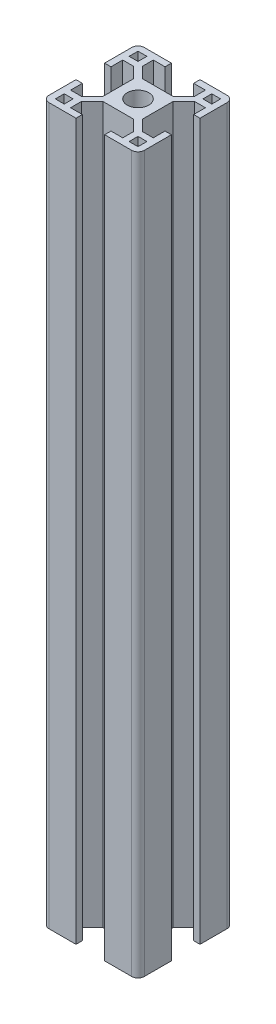
SolidWorks part; units mm, degrees
ref_plane "Front plane" through (0, 0, 0) normal (0, 0, 1) x (1, 0, 0)
ref_plane "Top plane" through (0, 0, 0) normal (0, 1, 0) x (1, 0, 0)
ref_plane "Right plane" through (0, 0, 0) normal (1, 0, 0) x (0, 0, -1)
ref_axis "Axis X" through (0, 0, 0) along (1, 0, 0)
ref_axis "Axis Y" through (0, 0, 0) along (0, 1, 0)
ref_axis "Axis Z" through (0, 0, 0) along (0, 0, 1)
sketch "Sketch1" plane through (0, 0, 0) normal (0, 1, 0) x (1, 0, 0)
  line L1 (-10, 10) -> (10, 10)
  line L2 (-10, 10) -> (-10, -10)
  line L3 (-10, -10) -> (10, -10)
  line L4 (10, 10) -> (10, -10)
  line L5 (-10, 10) -> (10, -10) construction
  line L6 (-10, -10) -> (10, 10) construction
  point P0 (0, 0)
  dimension "D1" = 20
  dimension "D2" = 20
extrude "Extrude1" add sketch "Sketch1" along normal blind 150
sketch "Sketch2" plane through (0, 150, 0) normal (0, 1, 0) x (1, 0, 0)
  line L0 (0, 0) -> (10, 0) construction
  line L1 (10, -10) -> (10, 10) construction
  line L2 (10, 10) -> (-10, 10) construction
  line L3 (8.6667, 3) -> (11.3333, 3)
  line L4 (8.6667, 3) -> (8.6667, -3) construction
  line L5 (8.6667, -3) -> (11.3333, -3)
  line L6 (11.3333, 3) -> (11.3333, -3)
  line L7 (8.6667, 3) -> (11.3333, -3) construction
  line L8 (8.6667, -3) -> (11.3333, 3) construction
  line L9 (6.8, 8.6667) -> (8.6667, 8.6667)
  line L10 (6.8, 8.6667) -> (6.8, 6.8)
  line L11 (6.8, 6.8) -> (8.6667, 6.8)
  line L12 (8.6667, 8.6667) -> (8.6667, 6.8)
  line L13 (6.8, 8.6667) -> (8.6667, 6.8) construction
  line L14 (6.8, 6.8) -> (8.6667, 8.6667) construction
  line L15 (0, 0) -> (10, 10) construction
  line L16 (8.6667, 3) -> (8.6667, 5.4667)
  line L17 (8.6667, 5.4667) -> (6.4095, 5.4667)
  line L18 (6.4095, 5.4667) -> (4.1333, 3.1905)
  line L19 (4.1333, 3.1905) -> (4.1333, -3.1905)
  line L20 (4.1333, -3.1905) -> (6.4095, -5.4667)
  line L21 (6.4095, -5.4667) -> (8.6667, -5.4667)
  line L22 (8.6667, -5.4667) -> (8.6667, -3)
  line L65 (-3.1905, 4.1333) -> (-5.4667, 6.4095)
  line L66 (-5.4667, 6.4095) -> (-5.4667, 8.6667)
  line L67 (-5.4667, 8.6667) -> (-3, 8.6667)
  line L68 (3, 11.3333) -> (-3, 11.3333)
  line L69 (-3, 8.6667) -> (-3, 11.3333)
  line L70 (3, 8.6667) -> (3, 11.3333)
  line L71 (3, 8.6667) -> (5.4667, 8.6667)
  line L72 (5.4667, 8.6667) -> (5.4667, 6.4095)
  line L73 (5.4667, 6.4095) -> (3.1905, 4.1333)
  line L74 (3.1905, 4.1333) -> (-3.1905, 4.1333)
  line L75 (0, 10) -> (0, -10) construction
  line L76 (-10, -10) -> (10, -10) construction
  line L77 (0, 0) -> (-10, 0) construction
  line L78 (-10, 10) -> (-10, -10) construction
  line L79 (8.6667, -8.6667) -> (8.6667, -6.8)
  line L80 (6.8, -6.8) -> (8.6667, -6.8)
  line L81 (6.8, -8.6667) -> (6.8, -6.8)
  line L82 (6.8, -8.6667) -> (8.6667, -8.6667)
  line L83 (-6.8, 6.8) -> (-8.6667, 6.8)
  line L84 (-8.6667, 8.6667) -> (-8.6667, 6.8)
  line L85 (-6.8, 8.6667) -> (-8.6667, 8.6667)
  line L86 (-6.8, 8.6667) -> (-6.8, 6.8)
  line L87 (-6.8, -8.6667) -> (-8.6667, -8.6667)
  line L88 (-6.8, -8.6667) -> (-6.8, -6.8)
  line L89 (-6.8, -6.8) -> (-8.6667, -6.8)
  line L90 (-8.6667, -8.6667) -> (-8.6667, -6.8)
  line L91 (-6.4095, -5.4667) -> (-8.6667, -5.4667)
  line L92 (-4.1333, -3.1905) -> (-6.4095, -5.4667)
  line L93 (-4.1333, 3.1905) -> (-4.1333, -3.1905)
  line L94 (-6.4095, 5.4667) -> (-4.1333, 3.1905)
  line L95 (-8.6667, 5.4667) -> (-6.4095, 5.4667)
  line L96 (-8.6667, 3) -> (-8.6667, 5.4667)
  line L97 (-8.6667, 3) -> (-11.3333, 3)
  line L98 (-11.3333, 3) -> (-11.3333, -3)
  line L99 (-8.6667, -3) -> (-11.3333, -3)
  line L100 (-8.6667, -5.4667) -> (-8.6667, -3)
  line L101 (3.1905, -4.1333) -> (-3.1905, -4.1333)
  line L102 (5.4667, -6.4095) -> (3.1905, -4.1333)
  line L103 (5.4667, -8.6667) -> (5.4667, -6.4095)
  line L104 (3, -8.6667) -> (5.4667, -8.6667)
  line L105 (3, -8.6667) -> (3, -11.3333)
  line L106 (3, -11.3333) -> (-3, -11.3333)
  line L107 (-3, -8.6667) -> (-3, -11.3333)
  line L108 (-5.4667, -8.6667) -> (-3, -8.6667)
  line L109 (-5.4667, -6.4095) -> (-5.4667, -8.6667)
  line L110 (-3.1905, -4.1333) -> (-5.4667, -6.4095)
  circle A0 centre (0, 0) radius 2.2667
  point P9 (7.7333, 7.7333)
  point P20 (7.5381, 5.4667)
  point P27 (10, -3)
  point P34 (-3, 10)
  point P37 (5.4667, 7.5381)
  dimension "D10" = 4.5333
  dimension "D1" = 2.6667
  dimension "D2" = 6
  dimension "D3" = 1.3333
  dimension "D4" = 1.3333
  dimension "D5" = 4.5333
  dimension "D6" = 5.4667
  dimension "D7" = 0.6667
  dimension "D8" = 1.3333
extrude "Extrude2" cut sketch "Sketch2" against normal through all
fillet "Fillet1" radius 1.3333 4 edges at (10, 75, 10) (10, 75, -10) (-10, 75, 10) (-10, 75, -10)
sketch "Эскиз3" plane through (0, 0, 0) normal (0, 0, 1) x (1, 0, 0)
  line L0 (0, 150) -> (0, 0) construction
  line L1 (3.1905, 150) -> (-3.1905, 150) construction
  line L2 (3.1905, 0) -> (-3.1905, 0) construction
  line L4 (-2.5, 77.5) -> (2.5, 77.5)
  line L5 (-2.5, 77.5) -> (-2.5, 72.5)
  line L6 (-2.5, 72.5) -> (2.5, 72.5)
  line L7 (2.5, 77.5) -> (2.5, 72.5)
  line L8 (-2.5, 77.5) -> (2.5, 72.5) construction
  line L9 (-2.5, 72.5) -> (2.5, 77.5) construction
  point P6 (0, 75)
  dimension "D1" = 5
  dimension "D2" = 5
extrude "Вырез-Вытянуть1" cut sketch "Эскиз3" against normal mid plane 20
equation "\"prof_width\"= 20'Aluminium profile parameters"
equation "\"D1@Sketch1\"=\"prof_width\""
equation "\"D2@Sketch1\"=\"prof_width\""
equation "\"prof_groove\"= 6"
equation "\"prof_length\"= 150"
equation "\"D1@Extrude1\"=\"prof_length\""
equation "\"D1@Sketch2\"=\"prof_width\"/30*4"
equation "\"D2@Sketch2\"=\"prof_groove\""
equation "\"D3@Sketch2\"=\"D1@Sketch2\"/2"
equation "\"D4@Sketch2\"=\"D3@Sketch2\""
equation "\"D5@Sketch2\"=\"prof_width\"/30*6.8"
equation "\"D6@Sketch2\"=\"prof_width\"/30*8.2"
equation "\"D7@Sketch2\"=\"D3@Sketch2\"/2"
equation "\"D8@Sketch2\"=\"D3@Sketch2\""
equation "\"D10@Sketch2\"=\"prof_width\"/30*6.8"
equation "\"D1@Fillet1\"=\"prof_width\"/30*2"
